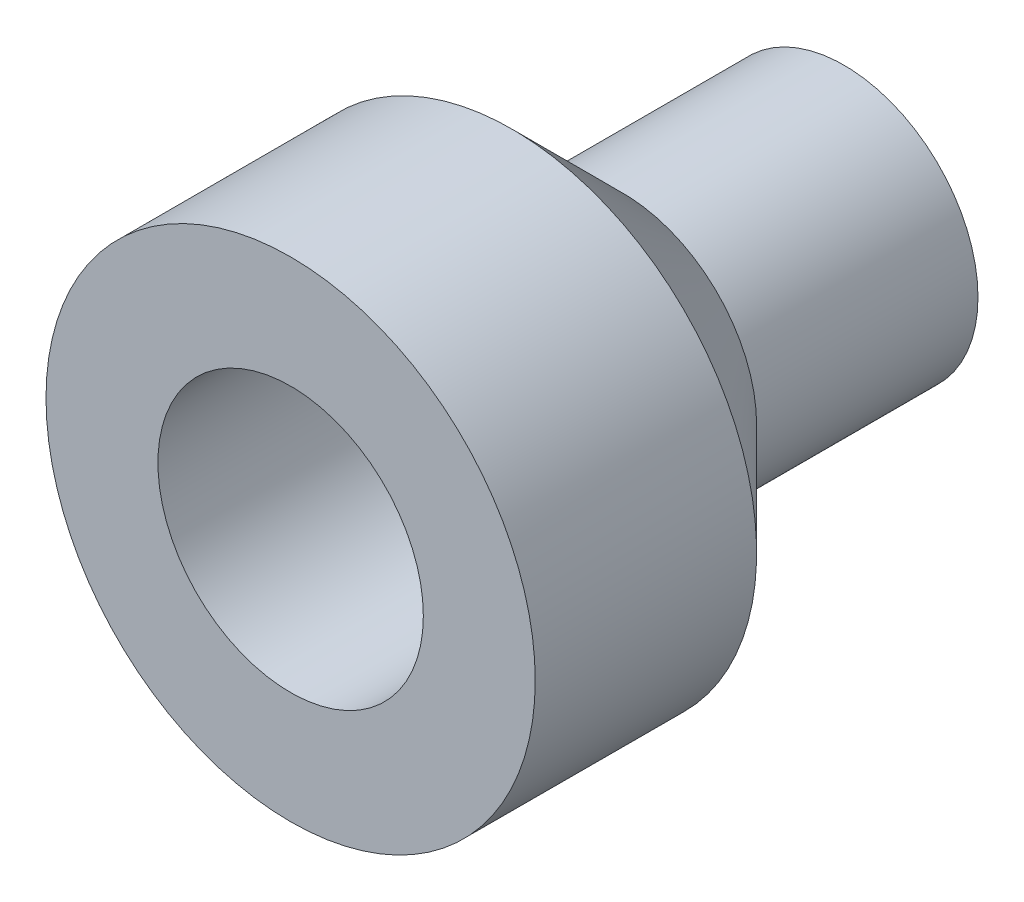
SolidWorks part; units mm, degrees
ref_plane "Front Plane" through (0, 0, 0) normal (0, 0, 1) x (1, 0, 0)
ref_plane "Top Plane" through (0, 0, 0) normal (0, 1, 0) x (1, 0, 0)
ref_plane "Right Plane" through (0, 0, 0) normal (1, 0, 0) x (0, 0, -1)
sketch "Sketch1" plane through (0, 0, 0) normal (0, 0, 1) x (1, 0, 0)
  circle A2 centre (0, 0) radius 6.05
  circle A3 centre (0, 0) radius 11.05
  dimension "D1" = 12.1
  dimension "D2" = 5
extrude "Boss-Extrude1" add sketch "Sketch1" along normal blind 10
sketch "Sketch2" plane through (0, 0, 0) normal (0, 0, -1) x (-1, 0, 0)
  circle A0 centre (0, 0) radius 6.05
extrude "Boss-Extrude2" add sketch "Sketch2" along normal blind 15 separate body
sketch "Sketch3" plane through (0, 0, 0) normal (0, 0, -1) x (-1, 0, 0)
  circle A0 centre (0, 0) radius 11.05
  circle A1 centre (0, 0) radius 6.05 construction
  dimension "D1" = 5
extrude "Boss-Extrude3" add sketch "Sketch3" along normal blind 5
chamfer "Chamfer1" distance 5 angle 45 1 edges at (-11.05, 0, -5)
sketch "Sketch4" plane through (0, 0, 10) normal (0, 0, 1) x (1, 0, 0)
  circle A2 centre (0, 0) radius 6.05
  circle A3 centre (0, 0) radius 5.995
  dimension "D1" = 11.99
extrude "Boss-Extrude4" add sketch "Sketch4" against normal blind 10
equation "\"a\"=12.1"
